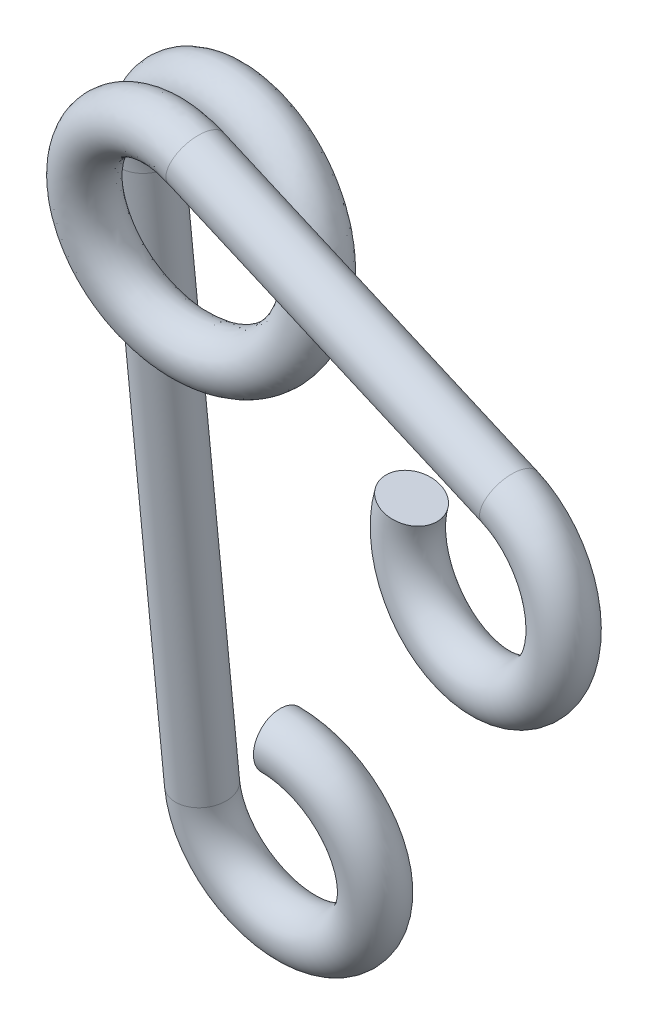
SolidWorks part; units mm, degrees
note: '?' marks a value the reader was unsure of.
ref_plane "Front Plane" through (0, 0, 0) normal (0, 0, 1) x (1, 0, 0)
ref_plane "Top Plane" through (0, 0, 0) normal (0, 1, 0) x (1, 0, 0)
ref_plane "Right Plane" through (0, 0, 0) normal (1, 0, 0) x (0, 0, -1)
sketch "Sketch1" plane through (0, 0, 0) normal (0, 0, 1) x (1, 0, 0)
  circle A0 centre (0, 0) radius 2.925
  dimension "D1" = 5.85
curve "Helix/Spiral1" pitch 1.7792 height 2.304 radius 2.925 left hand yes centre (0, 0, 0) axis (0, 0, 1) start towards (1, 0, 0)
sweep "Sweep1" add path "Helix/Spiral1" circular profile diameter 1.544 parameters "D3"=1.544
sketch "Sketch7" plane through (0, 0, 0) normal (0, -0.9953, -0.0964) x (1, 0, 0)
  line L0 (-3.697, 0) -> (-2.153, 0) construction
  circle A0 centre (-2.925, 0) radius 0.772 construction
  circle A1 centre (-2.925, 0) radius 0.772
extrude "Boss-Extrude1" add sketch "Sketch7" along normal blind 16.8
sketch "Sketch8" plane through (0.2122, -0.0616, 0.0214) normal (0.9559, -0.2774, 0.0964) x (0.0935, -0.0234, -0.9953)
  line L0 (-2.2831, 2.1611) -> (-2.2831, 3.7051) construction
  circle A0 centre (-2.2831, 2.9331) radius 0.772 construction
  circle A1 centre (-2.2831, 2.9331) radius 0.772
extrude "Boss-Extrude2" add sketch "Sketch8" along normal blind 10.57
ref_axis "Axis1" through (-2.925, -16.8692, -1.6331) along (0, 0.9953, 0.0964)?
ref_plane "Plane1" through (0, 0, 0) normal (0, -0.0964, 0.9953) x (1, 0, 0)
ref_axis "Axis2" through (10.2186, 0.0802, 3.2522) along (-0.9559, 0.2774, -0.0964)?
ref_plane "Plane2" through (-0.2135, 0.0535, 2.2725) normal (0.0935, -0.0234, -0.9953) x (-0.9956, -0.002, -0.0935)
sketch "Sketch10" plane through (0, 0, 0) normal (0, -0.0964, 0.9953) x (1, 0, 0)
  line L0 (-3.697, -16.8) -> (-2.153, -16.8) construction
  line L1 (-3.697, -16.8) -> (-2.153, -16.8) construction
  line L2 (-2.925, -16.9481) -> (-2.925, 0.1481) construction
  line L3 (-2.925, -16.8) -> (-0.425, -16.8) construction
  line L4 (-0.425, -16.8) -> (-0.425, -14.3) construction
  arc A0 (-2.925, -16.8) -> (-0.425, -14.3) centre (-0.425, -16.8) ccw
  dimension "D2" = 2.5
  dimension "D1" = 90
sketch "Sketch11" plane through (0, -16.7218, -1.6188) normal (0, -0.9953, -0.0964) x (1, 0, 0)
  circle A0 centre (-2.925, 0) radius 0.772 construction
  circle A1 centre (-2.925, 0) radius 0.772
sweep "Sweep2" add profiles "Sketch11" path "Sketch10"
sketch "Sketch12" plane through (-0.2135, 0.0535, 2.2725) normal (0.0935, -0.0234, -0.9953) x (-0.9956, -0.002, -0.0935)
  line L0 (-11.3974, 0.5426) -> (-10.9661, -0.9399) construction
  line L1 (-11.3974, 0.5426) -> (-10.9661, -0.9399) construction
  line L2 (-10.4781, 0.0061) -> (-1.716, 2.5555) construction
  line L3 (-11.1818, -0.1987) -> (-10.4833, -2.5991) construction
  line L4 (-10.4833, -2.5991) -> (-8.0829, -1.9007) construction
  arc A0 (-11.1818, -0.1987) -> (-8.0829, -1.9007) centre (-10.4833, -2.5991) ccw
  dimension "D2" = 2.5
  dimension "D1" = 90
sketch "Sketch13" plane through (10.3162, -2.9938, 1.0399) normal (0.9559, -0.2774, 0.0964) x (0.0935, -0.0234, -0.9953)
  circle A0 centre (-2.2831, 2.9331) radius 0.772 construction
  circle A1 centre (-2.2831, 2.9331) radius 0.772
sweep "Sweep3" add profiles "Sketch13" path "Sketch12"
equation "\"D_coil\"=0.005850"
equation "\"d_wire\"=0.001544"
equation "\"Nb\"=1.294954"
equation "\"loop_diam\"=0.005000"
equation "\"height\"=0.002304"
equation "\"l_i_arm\"=0.010570"
equation "\"l_p_arm\"=0.016800"
equation "\"D1@Sketch1\"=\"D_coil\"*1000"
equation "\"D3@Helix/Spiral1\"=\"height\"*1000"
equation "\"D5@Helix/Spiral1\"=\"Nb\""
equation "\"D3@Sweep1\"=\"d_wire\"*1000"
equation "\"D1@Boss-Extrude1\"=\"l_p_arm\"*1000"
equation "\"D1@Boss-Extrude2\"=\"l_i_arm\"*1000"
equation "\"D2@Sketch10\"=\"loop_diam\"*1000/2"
equation "\"D2@Sketch12\"=\"loop_diam\"*1000/2"
